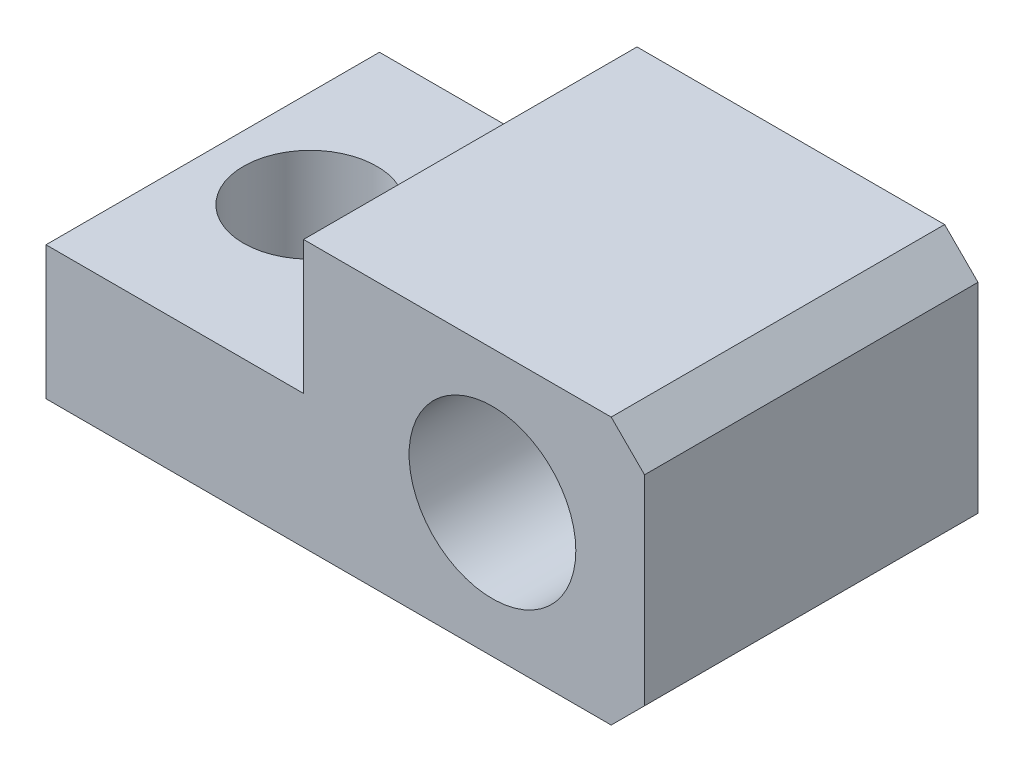
SolidWorks part; units mm, degrees
ref_plane "Спереди" through (0, 0, 0) normal (0, 0, 1) x (1, 0, 0)
ref_plane "Сверху" through (0, 0, 0) normal (0, 1, 0) x (1, 0, 0)
ref_plane "Справа" through (0, 0, 0) normal (1, 0, 0) x (0, 0, -1)
sketch "Эскиз1" plane through (0, 0, 0) normal (0, 0, 1) x (1, 0, 0)
  line L0 (3.5608, 4) -> (4.5608, 3)
  line L1 (-5.6654, 4) -> (3.5608, 4)
  line L2 (-13.389, 0) -> (-13.389, -4)
  line L3 (-13.389, -4) -> (3.5608, -4)
  line L4 (4.5608, 3) -> (4.5608, -3)
  line L5 (3.5608, -4) -> (4.5608, -3)
  line L8 (-5.6654, 0) -> (-13.389, 0)
  line L9 (-5.6654, 0) -> (-5.6654, 4)
  circle A0 centre (0, 0) radius 2.5
  point P3 (4.5608, -4)
  point P6 (4.5608, 4)
  dimension "D3" = 1
  dimension "D4" = 1
extrude "Вытянуть1" add sketch "Эскиз1" along normal blind 10
sketch "Эскиз2" plane through (0, 0, 0) normal (0, 1, 0) x (-1, 0, 0)
  circle A0 centre (10.4668, 5) radius 2
extrude "Вытянуть2" cut sketch "Эскиз2" against normal through all
